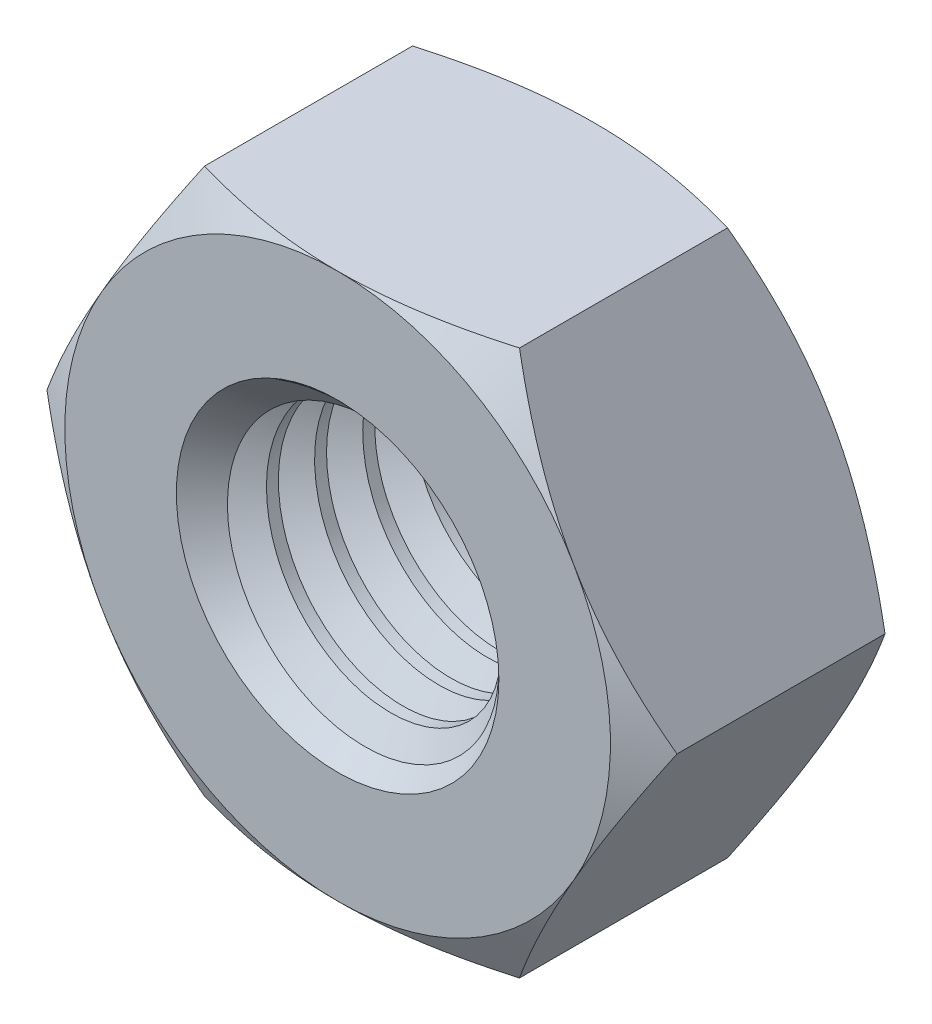
SolidWorks part; units mm, degrees
ref_plane "Front" through (0, 0, 0) normal (0, 0, 1) x (1, 0, 0)
ref_plane "Top" through (0, 0, 0) normal (0, 1, 0) x (1, 0, 0)
ref_plane "Right" through (0, 0, 0) normal (1, 0, 0) x (0, 0, -1)
sketch "Çizim1" plane through (0, 0, 0) normal (0, 0, 1) x (1, 0, 0)
  line L1 (9.815, 0) -> (4.9075, 8.5)
  line L2 (4.9075, 8.5) -> (-4.9075, 8.5)
  line L3 (-4.9075, 8.5) -> (-9.815, 0)
  line L4 (-9.815, 0) -> (-4.9075, -8.5)
  line L5 (-4.9075, -8.5) -> (4.9075, -8.5)
  line L6 (4.9075, -8.5) -> (9.815, 0)
  circle A0 centre (0, 0) radius 8.5 construction
  dimension "D1" = 17
extrude "Yükseklik-Ekstrüzyon1" add sketch "Çizim1" along normal blind 8
sketch "Çizim2" plane through (0, 0, 8) normal (0, 0, 1) x (1, 0, 0)
  circle A0 centre (0, 0) radius 8.5
extrude "Kes-Ekstrüzyon1" cut sketch "Çizim2" against normal blind 8 draft 60 flip side to cut
sketch "Çizim3" plane through (0, 0, 0) normal (0, 0, -1) x (-1, 0, 0)
  circle A0 centre (0, 0) radius 8.5
extrude "Kes-Ekstrüzyon2" cut sketch "Çizim3" against normal blind 8 draft 60 flip side to cut
sketch "Çizim4" plane through (0, 0, 0) normal (0, 0, -1) x (-1, 0, 0)
  circle A0 centre (0, 0) radius 4.025
  dimension "D1" = 8.05
extrude "Kes-Ekstrüzyon3" cut sketch "Çizim4" against normal blind 28
sketch "Çizim5" plane through (0, 0, 0) normal (0, 0, -1) x (-1, 0, 0)
  circle A0 centre (0, 0) radius 4.025
curve "Helis/Spiral1" pitch 1.5 height 10 radius 4.025 centre (0, 0, 0) axis (0, 0, 1) start towards (1, 0, 0)
ref_plane "Düzlem1" through (-2.0125, -3.4858, 10) normal (0.8645, -0.4991, 0.0592) x (0.0513, -0.0296, -0.9982)
chamfer "Pah1" distance 1 angle 45 2 edges at (-4.025, 0, 0) (4.025, 0, 8)
sketch "Çizim6" plane through (-2.0125, -3.4858, 10) normal (0.8645, -0.4991, 0.0592) x (0.0513, -0.0296, -0.9982)
  line L0 (0.7416, 0.3096) -> (-0.7416, 0.3096)
  line L1 (0, -0.975) -> (0.7416, 0.3096)
  line L3 (-0.7416, 0.3096) -> (0, -0.975)
  line L5 (0, 0.4875) -> (-0.8444, 0.4875) [skipped]
  circle A0 centre (0, 0) radius 0.4875 construction
  dimension "D1" = 0.975
sweep "Kes-Süpür1" cut profiles "Çizim6" path "Helis/Spiral1" align with end faces yes
